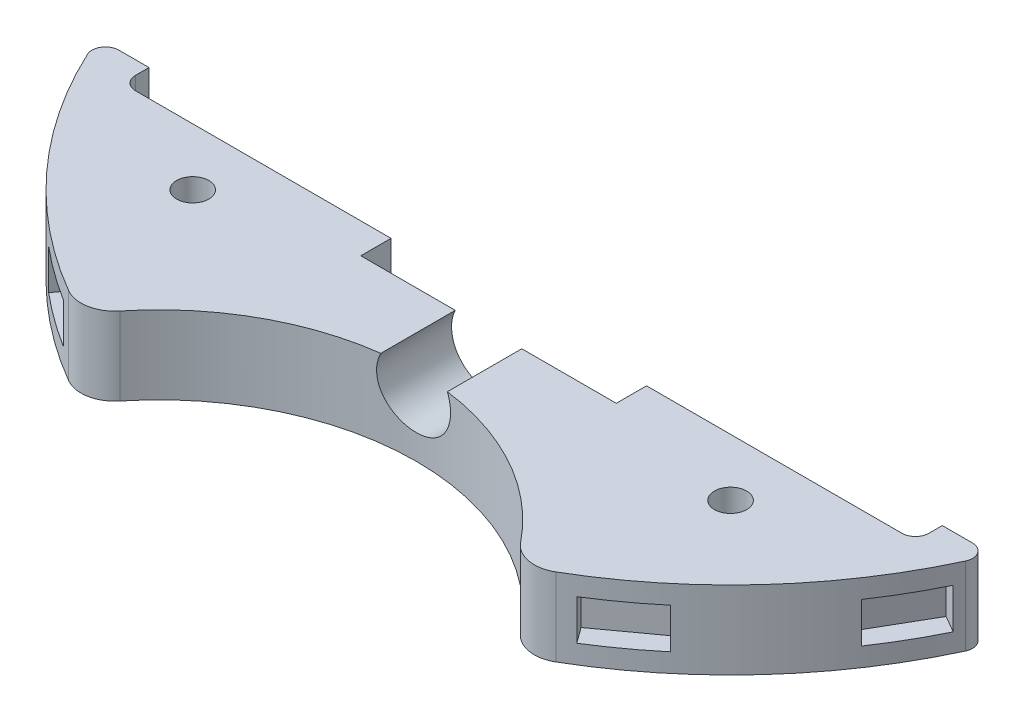
SolidWorks part; units mm, degrees
material "ABS"
ref_plane "Front Plane" through (0, 0, 0) normal (0, 0, 1) x (1, 0, 0)
ref_plane "Top Plane" through (0, 0, 0) normal (0, 1, 0) x (1, 0, 0)
ref_plane "Right Plane" through (0, 0, 0) normal (1, 0, 0) x (0, 0, -1)
sketch "Sketch1" plane through (0, 0, 0) normal (0, 1, 0) x (1, 0, 0)
  line L0 (0, -85) -> (-32.2211, -64.3879) construction
  line L1 (0, -85) -> (0, 0) construction
  arc A0 (36.2245, -62.2237) -> (-36.2245, -62.2237) centre (0, 0) ccw
  arc A1 (29.8119, -61.0352) -> (-29.8119, -61.0352) centre (0, -85) ccw
  arc A2 (36.2245, -62.2237) -> (29.8119, -61.0352) centre (33.7089, -57.9026) cw
  arc A3 (-29.8119, -61.0352) -> (-36.2245, -62.2237) centre (-33.7089, -57.9026) cw
  dimension "D1" = 144
  dimension "D2" = 76.5
  dimension "D4" = 5
  dimension "D3" = 85
extrude "Boss-Extrude1" add sketch "Sketch1" along normal mid plane 11.6
sketch "solenoid placement" plane through (0, 5.8, 0) normal (0, 1, 0) x (1, 0, 0)
  line L0 (0, 0) -> (0, -36) construction
  line L5 (-19, -36) -> (19, -36)
  line L7 (19, -36) -> (19, 28)
  line L9 (19, 28) -> (-19, 28)
  line L11 (-19, 28) -> (-19, -36)
  circle A1 centre (0, 0) radius 72 construction
  arc A2 (36.2245, -62.2237) -> (-36.2245, -62.2237) centre (0, 0) ccw construction
  point P7 (0, 28)
  dimension "D1" = 38
  dimension "D2" = 64
  dimension "D3" = 36
extrude "Cut-Extrude1" cut sketch "solenoid placement" against normal through all
sketch "Sketch6" plane through (0, 5.8, 0) normal (0, 1, 0) x (1, 0, 0)
  line L0 (0, 0) -> (0, -46.75) construction
  arc A0 (29.8119, -61.0352) -> (-29.8119, -61.0352) centre (0, -85) ccw construction
  circle A1 centre (40, -40) radius 2.4
  circle A4 centre (-40, -40) radius 2.4
  dimension "D1" = 4.8
  dimension "D2" = 40
  dimension "D3" = 40
extrude "Cut-Extrude6" cut sketch "Sketch6" against normal through all
sketch "Sketch3" plane through (0, 5.8, 0) normal (0, 1, 0) x (1, 0, 0)
  line L0 (-72, -27.5) -> (-59, -27.5)
  line L1 (-59, -31.5) -> (59, -31.5)
  line L2 (-72, -27.5) -> (-72, 31.5)
  line L3 (-59, -27.5) -> (-59, -31.5)
  line L4 (72, -27.5) -> (72, 31.5)
  line L5 (-72, 31.5) -> (72, 31.5) construction
  line L6 (0, 31.5) -> (0, -31.5) construction
  line L7 (59, -27.5) -> (59, -31.5)
  line L8 (-72, 31.5) -> (-72, 72)
  line L9 (72, -27.5) -> (59, -27.5)
  line L10 (-72, 72) -> (72, 72)
  line L11 (72, 31.5) -> (72, 72)
  arc A0 (36.2245, -62.2237) -> (-36.2245, -62.2237) centre (0, 0) ccw construction
  arc A1 (36.2245, -62.2237) -> (-36.2245, -62.2237) centre (0, 0) ccw construction
  point P0 (0, 0)
  dimension "D2" = 4
  dimension "D1" = 63
  dimension "D3" = 13
extrude "Cut-Extrude3" cut sketch "Sketch3" against normal through all
fillet "Fillet1" radius 2 4 edges at (66.5413, 0, 27.5) (59, 0, 31.5) (-66.5413, 0, 27.5) (-59, 0, 31.5)
sketch "Sketch8" plane through (0, 0, 0) normal (0, 1, 0) x (1, 0, 0)
  line L0 (0, 0) -> (62.3538, -36) construction
  line L1 (0, 0) -> (42.3205, -58.2492) construction
  line L2 (0, 0) -> (14.9696, -70.4266) construction
  line L3 (0, 0) -> (-14.9696, -70.4266) construction
  line L4 (-42.3205, -58.2492) -> (0, 0) construction
  line L5 (0, 0) -> (-62.3538, -36) construction
  line L6 (0, 0) -> (0, -72) construction
  arc A0 (-62.3538, -36) -> (-42.3205, -58.2492) centre (0, 0) ccw construction
  arc A1 (62.3538, -36) -> (42.3205, -58.2492) centre (0, 0) cw construction
  arc A2 (14.9696, -70.4266) -> (42.3205, -58.2492) centre (0, 0) ccw construction
  arc A3 (14.9696, -70.4266) -> (-14.9696, -70.4266) centre (0, 0) cw construction
  arc A4 (-14.9696, -70.4266) -> (-42.3205, -58.2492) centre (0, 0) cw construction
  arc A5 (36.2245, -62.2237) -> (65.294, -30.3429) centre (0, 0) ccw construction
  dimension "D1" = 120
sketch "Sketch9" plane through (0, 0, 0) normal (0, 1, 0) x (1, 0, 0)
  line L0 (0, 0) -> (-59.7033, -40.2432) construction
  line L1 (0, 0) -> (-64.7033, -31.583) construction
  line L2 (-64.7033, -31.583) -> (-59.7033, -40.2432) construction
  line L3 (-64.7033, -31.583) -> (-62.1918, -30.133)
  line L4 (-62.1918, -30.133) -> (-57.1918, -38.7932)
  line L5 (-57.1918, -38.7932) -> (-59.7033, -40.2432)
  line L6 (-46.2635, -55.1697) -> (-44.5589, -52.8235)
  line L7 (-44.5589, -52.8235) -> (-36.4687, -58.7014)
  line L8 (-36.4687, -58.7014) -> (-38.1733, -61.0475)
  line L9 (0, 0) -> (-38.1733, -61.0475) construction
  line L10 (0, 0) -> (-46.2635, -55.1697) construction
  line L11 (-46.2635, -55.1697) -> (-38.1733, -61.0475) construction
  line L12 (-19.8242, -69.217) -> (-19.2213, -66.3804) [skipped]
  line L13 (-19.2213, -66.3804) -> (-9.4398, -68.4595) [skipped]
  line L14 (-9.4398, -68.4595) -> (-10.0428, -71.2962) [skipped]
  line L15 (0, 0) -> (-10.0428, -71.2962) construction
  line L16 (0, 0) -> (-19.8242, -69.217) construction
  line L17 (-19.8242, -69.217) -> (-10.0428, -71.2962) construction
  line L18 (10.0428, -71.2962) -> (9.4398, -68.4595) [skipped]
  line L19 (9.4398, -68.4595) -> (19.2213, -66.3804) [skipped]
  line L20 (19.2213, -66.3804) -> (19.8242, -69.217) [skipped]
  line L21 (0, 0) -> (19.8242, -69.217) construction
  line L22 (0, 0) -> (10.0428, -71.2962) construction
  line L23 (10.0428, -71.2962) -> (19.8242, -69.217) construction
  line L24 (38.1733, -61.0475) -> (36.4687, -58.7014)
  line L25 (36.4687, -58.7014) -> (44.5589, -52.8235)
  line L26 (44.5589, -52.8235) -> (46.2635, -55.1697)
  line L27 (0, 0) -> (46.2635, -55.1697) construction
  line L28 (0, 0) -> (38.1733, -61.0475) construction
  line L29 (38.1733, -61.0475) -> (46.2635, -55.1697) construction
  line L30 (59.7033, -40.2432) -> (57.1918, -38.7932)
  line L31 (57.1918, -38.7932) -> (62.1918, -30.133)
  line L32 (62.1918, -30.133) -> (64.7033, -31.583)
  line L33 (0, 0) -> (64.7033, -31.583) construction
  line L34 (0, 0) -> (59.7033, -40.2432) construction
  line L35 (59.7033, -40.2432) -> (64.7033, -31.583) construction
  arc A0 (-59.7033, -40.2432) -> (-64.7033, -31.583) centre (0, 0) cw
  arc A1 (-62.3538, -36) -> (-42.3205, -58.2492) centre (0, 0) ccw construction
  arc A2 (-38.1733, -61.0475) -> (-46.2635, -55.1697) centre (0, 0) cw
  arc A3 (-10.0428, -71.2962) -> (-19.8242, -69.217) centre (0, 0) cw [skipped]
  arc A4 (19.8242, -69.217) -> (10.0428, -71.2962) centre (0, 0) cw [skipped]
  arc A5 (46.2635, -55.1697) -> (38.1733, -61.0475) centre (0, 0) cw
  arc A6 (64.7033, -31.583) -> (59.7033, -40.2432) centre (0, 0) cw
  point P5 (0, 0)
  point P8 (-62.3538, -36)
  point P12 (62.3538, -36)
  point P34 (0, 0)
  dimension "D1" = 10
  dimension "D2" = 2.9
  dimension "D3" = 6
extrude "Cut-Extrude7" cut sketch "Sketch9" against normal mid plane 6
sketch "Sketch11" plane through (0, 0, 36) normal (0, 0, -1) x (-1, 0, 0)
  line L0 (0, -5.8) -> (0, 3.4) construction
  line L1 (19, -5.8) -> (-19, -5.8) construction
  circle A0 centre (0, 3.4) radius 5.5
  dimension "D2" = 11
  dimension "D1" = 9.2
extrude "Cut-Extrude8" cut sketch "Sketch11" against normal through all
equation "\"smallPulleyTeeth\"= 15"
equation "\"largePulleyTeeth\"= 30"
equation "\"eighthThick\"= 2.9mm"
equation "\"sixteenthThick\" = 1.7mm"
equation "\"quarterThick\"=6.0mm"
equation "\"OD\" = 146mm"
equation "\"puckAngle\" = 60.5deg"
equation "\"puckDiam\" = 76.5mm"
equation "\"D2@Sketch1\"=\"puckDiam\""
equation "\"D1@Boss-Extrude1\"=\"eighthThick\"*4"
equation "\"axlePress\" = 5.9mm"
equation "\"press\" = 0.2mm"
equation "\"wheelClear\" = 0.3mm"
equation "\"10-32clear\" = 4.8mm"
equation "\"6-32clear\" = 3.3mm"
equation "\"8-32clear\" = 4.0mm"
equation "\"wheelHeight\" = 22mm"
equation "\"wheelWell\" = 65mm"
equation "\"puckDist\" = 85mm"
equation "\"scoopFillet\" = 5mm"
equation "\"4-40clear\" = 3.0mm"
equation "\"D3@Sketch1\"=\"puckDist\""
equation "\"D4@Sketch1\"=\"scoopFillet\""
equation "\"D1@Sketch6\"=\"10-32clear\""
equation "\"D2@Sketch9\"=\"eighthThick\""
